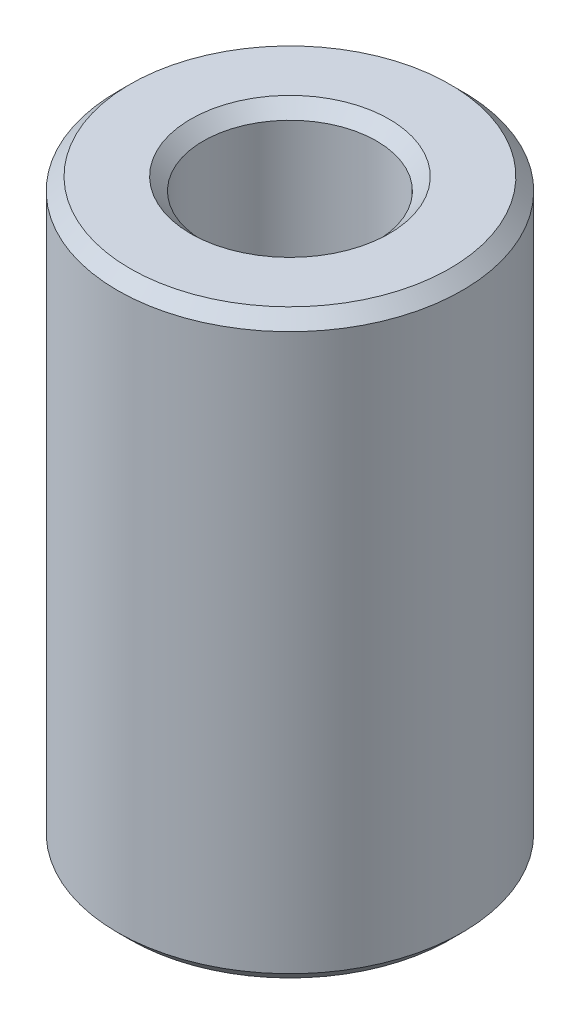
SolidWorks part; units mm, degrees
ref_plane "Front Plane" through (0, 0, 0) normal (0, 0, 1) x (1, 0, 0)
ref_plane "Top Plane" through (0, 0, 0) normal (0, 1, 0) x (1, 0, 0)
ref_plane "Right Plane" through (0, 0, 0) normal (1, 0, 0) x (0, 0, -1)
sketch "Sketch1" plane through (0, 0, 0) normal (0, 1, 0) x (1, 0, 0)
  circle A0 centre (0, 0) radius 37.5
  dimension "SLEEVE_OD" = 75
extrude "Boss-Extrude1" add sketch "Sketch1" along normal blind 126.4421
sketch "Sketch2" plane through (0, 0, 0) normal (0, 1, 0) x (1, 0, 0)
  circle A0 centre (0, 0) radius 18.8464
  dimension "BORE_D" = 37.6928
extrude "Cut-Extrude1" cut sketch "Sketch2" along normal through all
chamfer "Chamfer1" distance 2.7446 angle 45 4 edges at (0, 126.4421, 18.8464) (0, 0, 18.8464) (0, 0, 37.5) (0, 126.4421, 37.5)
